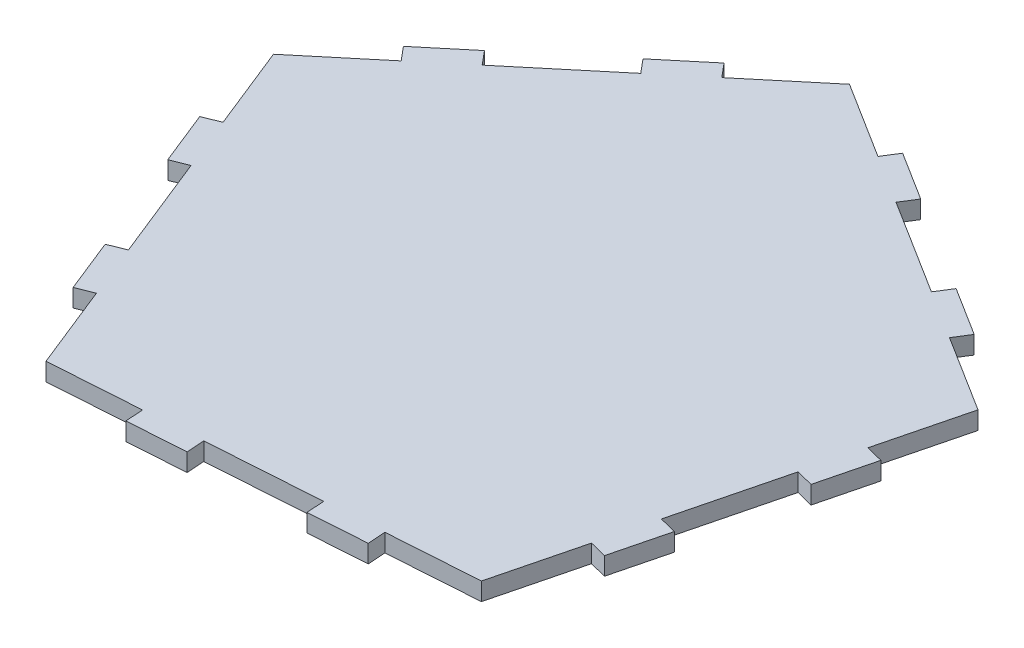
SolidWorks part; units mm, degrees
ref_plane "Front Plane" through (0, 0, 0) normal (0, 0, 1) x (1, 0, 0)
ref_plane "Top Plane" through (0, 0, 0) normal (0, 1, 0) x (1, 0, 0)
ref_plane "Right Plane" through (0, 0, 0) normal (1, 0, 0) x (0, 0, -1)
sketch "Sketch1" plane through (0, 0, 0) normal (0, 1, 0) x (1, 0, 0)
  line L1 (-63.7371, 16.0796) -> (-34.9884, -55.6487)
  line L2 (-34.9884, -55.6487) -> (42.1131, -50.4724)
  line L3 (42.1131, -50.4724) -> (61.0157, 24.4551)
  line L4 (61.0157, 24.4551) -> (-4.4033, 65.5865)
  line L5 (-4.4033, 65.5865) -> (-63.7371, 16.0796)
  circle A0 centre (0, 0) radius 53.18 construction
  dimension "D1" = 106.36
extrude "Boss-Extrude1" add sketch "Sketch1" along normal blind 3.18
sketch "Sketch2" plane through (0, 0, 0) normal (0, -1, 0) x (1, 0, 0)
  line L0 (-56.7215, 1.4244) -> (-53.7698, 0.2413)
  line L1 (-56.7215, 1.4244) -> (-53.0831, 10.5024)
  line L2 (-53.7698, 0.2413) -> (-50.1313, 9.3193)
  line L3 (-53.0831, 10.5024) -> (-50.1313, 9.3193)
  line L4 (-63.7371, -16.0796) -> (-34.9884, 55.6487) construction
  line L5 (-45.6425, 29.0668) -> (-42.004, 38.1448)
  line L6 (-45.6425, 29.0668) -> (-42.6907, 27.8837)
  line L7 (-42.004, 38.1448) -> (-39.0523, 36.9617)
  line L8 (-42.6907, 27.8837) -> (-39.0523, 36.9617)
  line L9 (-49.3628, 19.7846) -> (-19.2439, 7.7129) construction
  dimension "D1" = 3.18
  dimension "D2" = 9.78
  dimension "D3" = 10
extrude "Cut-Extrude1" [suppressed] cut sketch "Sketch2" against normal through all
ref_axis "Axis1" through (0, 3.339, 0) along (0, -1, 0)
pattern_circular "CirPattern1" [suppressed] count 5 over 360 about axis through (0, 3.339, 0) along (0, -1, 0) of bodies 102
sketch "Sketch3" plane through (0, 0, 0) normal (0, -1, 0) x (1, 0, 0)
  line L0 (-56.8852, 1.016) -> (-53.9335, -0.1671)
  line L1 (-56.8852, 1.016) -> (-53.0831, 10.5024)
  line L2 (-53.9335, -0.1671) -> (-50.1313, 9.3193)
  line L3 (-53.0831, 10.5024) -> (-50.1313, 9.3193)
  line L4 (-63.7371, -16.0796) -> (-34.9884, 55.6487) construction
  line L5 (-45.6425, 29.0668) -> (-42.6907, 27.8837)
  line L6 (-45.6425, 29.0668) -> (-41.8403, 38.5532)
  line L7 (-42.6907, 27.8837) -> (-38.8886, 37.3701)
  line L8 (-41.8403, 38.5532) -> (-38.8886, 37.3701)
  line L9 (0, 0) -> (-49.3628, 19.7846) construction
  line L10 (-65.563, -20.6353) -> (-62.6113, -21.8183)
  line L11 (-65.563, -20.6353) -> (-33.4497, 59.4878)
  line L12 (-62.6113, -21.8183) -> (-30.498, 58.3048)
  line L13 (-33.4497, 59.4878) -> (-30.498, 58.3048)
  line M14 (-63.7371, -16.0796) -> (-4.4033, -65.5865)
  line M17 (42.1131, 50.4724) -> (-34.9884, 55.6487)
  line M18 (-34.9884, 55.6487) -> (-63.7371, -16.0796)
  dimension "D1" = 10.22
  dimension "D2" = 10
  dimension "D3" = 3.18
  dimension "D4" = 3.18
extrude "Cut-Extrude2" cut sketch "Sketch3" against normal blind 10 contours L12 L0 M14 M18 | L12 L9 L11 L3 | L9 L12 L5 M18 | L8 L12 M17 M18 region at (-58.9188, 0, -8.3707) region at (-49.747, 0, 14.5519) region at (-46.0267, 0, 23.8342) region at (-36.8281, 0, 46.746)
pattern_circular "CirPattern2" count 5 over 360 about axis through (0, 3.339, 0) along (0, -1, 0) of "Cut-Extrude2"
equation "\"kerf\"= .22mm"
equation "\"tabWidth\"= 10 + \"kerf\" "
equation "\"tabSeperation\" = 10  "
equation "\"tabThickness\"= 3.18"
equation "\"D1@Sketch2\"=\"tabThickness\""
equation "\"D3@Sketch2\"=\"tabSeperation\""
equation "\"D2@Sketch3\"=\"tabSeperation\""
equation "\"D3@Sketch3\"=\"tabThickness\""
equation "\"D4@Sketch3\"=\"tabThickness\""
equation "\"tabLength\" = \"kerf\" + 12"
